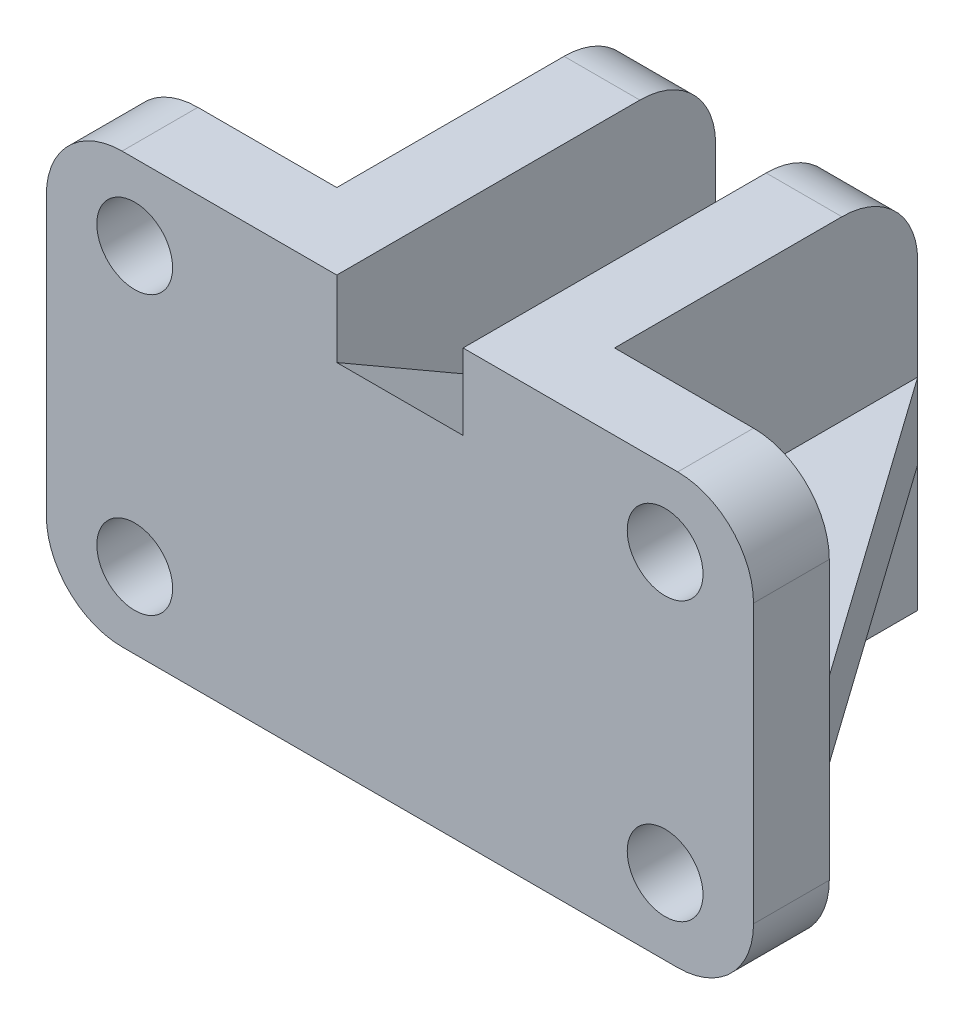
SolidWorks part; units mm, degrees
material "6061铝合金."
ref_plane "前视基准面" through (0, 0, 0) normal (0, 0, 1) x (1, 0, 0)
ref_plane "上视基准面" through (0, 0, 0) normal (0, 1, 0) x (1, 0, 0)
ref_plane "右视基准面" through (0, 0, 0) normal (1, 0, 0) x (0, 0, -1)
sketch "草图1" plane through (0, 0, 0) normal (0, 0, 1) x (1, 0, 0)
  line L1 (-14, 8.5) -> (14, 8.5)
  line L2 (-14, 8.5) -> (-14, -8.5)
  line L3 (-14, -8.5) -> (14, -8.5)
  line L4 (14, 8.5) -> (14, -8.5)
  line L5 (-14, 8.5) -> (14, -8.5) construction
  line L6 (-14, -8.5) -> (14, 8.5) construction
  point P0 (0, 0)
  dimension "D1" = 17
  dimension "D2" = 28
extrude "凸台-拉伸1" add sketch "草图1" along normal blind 3
sketch "草图3" plane through (0, 0, 0) normal (1, 0, 0) x (0, 0, -1)
  line L0 (0, 8.5) -> (12, 1.5718)
  line L1 (12, 1.5718) -> (0, 1.5718) construction
  line L2 (0, 1.5718) -> (0, 8.5)
  line L3 (12, 1.5718) -> (12, -6.5)
  line L4 (12, -6.5) -> (0, -6.5)
  line L5 (0, -8.5) -> (0, 8.5) construction
  line L6 (0, -6.5) -> (0, 1.5718)
  dimension "D1" = 30
  dimension "D2" = 15
  dimension "D3" = 12
extrude "凸台-拉伸2" add sketch "草图3" along normal mid plane 11
sketch "草图4" plane through (0, 0, 0) normal (1, 0, 0) x (0, 0, -1)
  line L0 (0, 8.5) -> (12, 1.5718)
  line L1 (12, 1.5718) -> (12, -3.1603)
  line L2 (-3, 8.5) -> (0, 8.5) construction
  line L3 (12, -3.1603) -> (0, 3.7679)
  line L4 (0, -8.5) -> (0, 8.5) construction
  line L6 (12, -6.5) -> (12, 1.5718) construction
  line L7 (0, 3.7679) -> (-3, 5.5)
  line L8 (-3, -8.5) -> (-3, 8.5) construction
  line L9 (0, 8.5) -> (-3, 10.2321)
  line L10 (-3, 10.2321) -> (-3, 5.5)
  dimension "D1" = 3
extrude "切除-拉伸1" cut sketch "草图4" against normal mid plane 5
ref_plane "基准面1" through (0, 0, 0) normal (0, 1, 0) x (1, 0, 0)
sketch "草图5" plane through (0, 0, 0) normal (0, 1, 0) x (1, 0, 0)
  line L0 (5.5, 12) -> (14, 0)
rib "筋4" sketch "草图5" sketch "草图5" thickness 3 extrusion direction parallel to sketch draft on no parameters "D1"=3
mirror "镜向1" about plane through (0, 0, 0) normal (1, 0, 0) of "筋4"
fillet "圆角1" radius 3 4 edges at (-14, 8.5, 1.5) (-14, -8.5, 1.5) (14, -8.5, 1.5) (14, 8.5, 1.5)
sketch "草图6" plane through (0, 0, 0) normal (0, 0, -1) x (-1, 0, 0)
  line L1 (-10.5, -5.5) -> (10.5, -5.5) construction
  line L2 (-10.5, -5.5) -> (-10.5, 5.5) construction
  line L3 (-10.5, 5.5) -> (10.5, 5.5) construction
  line L4 (10.5, -5.5) -> (10.5, 5.5) construction
  line L5 (-10.5, -5.5) -> (10.5, 5.5) construction
  line L6 (-10.5, 5.5) -> (10.5, -5.5) construction
  circle A0 centre (-10.5, 5.5) radius 1.5
  circle A1 centre (10.5, 5.5) radius 1.5
  circle A2 centre (10.5, -5.5) radius 1.5
  circle A3 centre (-10.5, -5.5) radius 1.5
  point P0 (0, 0)
  dimension "D3" = 3
  dimension "D4" = 3
  dimension "D5" = 3
  dimension "D6" = 3
  dimension "D1" = 11
  dimension "D2" = 21
extrude "切除-拉伸2" cut sketch "草图6" against normal blind 5.3
sketch "草图7" plane through (0, 0, 0) normal (1, 0, 0) x (0, 0, -1)
  line L0 (0, 8.5) -> (12, 8.5)
  line L1 (12, 8.5) -> (12, 1.5718)
  line L2 (0, 8.5) -> (12, 1.5718)
extrude "凸台-拉伸3" add sketch "草图7" along normal mid plane 11
extrude "切除-拉伸3" cut sketch "草图7<2>" against normal mid plane 5
sketch "草图7<2>" plane through (0, 0, 0) normal (1, 0, 0) x (0, 0, -1) same geometry as "草图7"
fillet "圆角3" radius 3 2 edges at (-4, 8.5, -12) (4, 8.5, -12)
fillet "圆角4" radius 10 1 edges at (0, -3.1603, -12)
